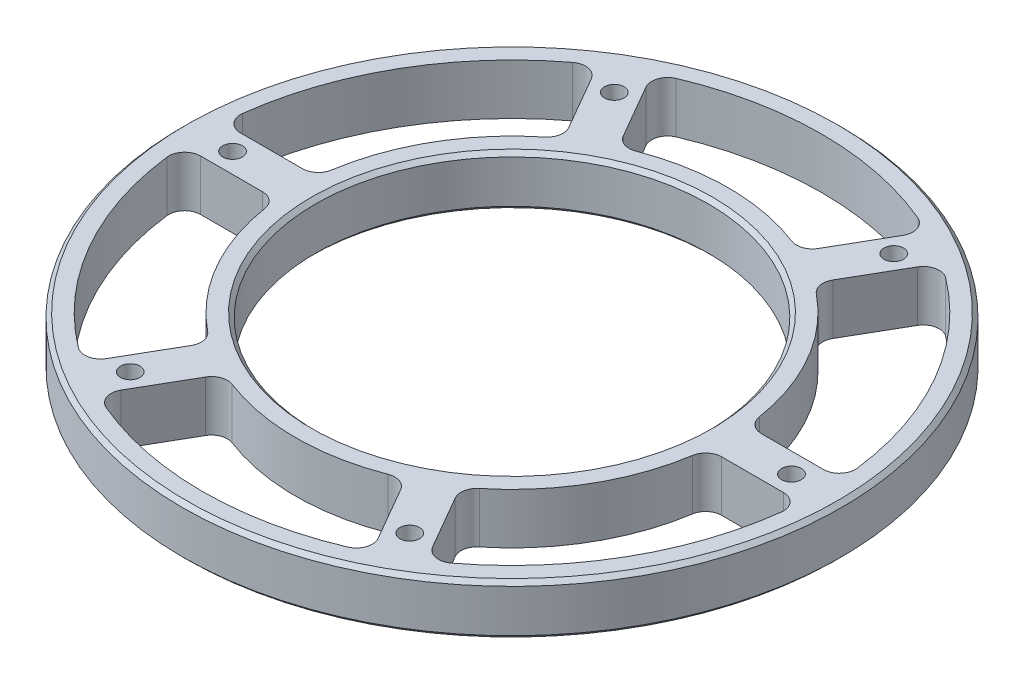
SolidWorks part; units mm, degrees
material "6061-T6 (SS)"
ref_plane "Front Plane" through (0, 0, 0) normal (0, 0, 1) x (1, 0, 0)
ref_plane "Top Plane" through (0, 0, 0) normal (0, 1, 0) x (1, 0, 0)
ref_plane "Right Plane" through (0, 0, 0) normal (1, 0, 0) x (0, 0, -1)
sketch "Sketch2" plane through (0, 0, 0) normal (1, 0, 0) x (0, 0, -1)
  line L0 (-49.2125, 0) -> (-82.55, 0)
  line L1 (-82.55, 0) -> (-82.55, 12.7)
  line L2 (-82.55, 12.7) -> (-49.2125, 12.7)
  line L3 (-49.2125, 12.7) -> (-49.2125, 0)
  dimension "D1" = 82.55
  dimension "D2" = 12.7
  dimension "D4" = 49.2125
ref_axis "Axis1" through (0, -0.635, 0) along (0, 1, 0)
revolve "Revolve1" add sketch "Sketch2" angle 360 about axis through (0, -0.635, 0) along (0, 1, 0)
hole_wizard "#10 (0.1935) Diameter Hole1" positions "Sketch6" profile "Sketch7" hole size "#10" standard "ANSI Inch" end condition through all
sketch "Sketch6" plane through (0, 12.7, 0) normal (0, 1, 0) x (1, 0, 0)
  line L0 (0, 0) -> (-69.8201, 120.932) construction
  line L2 (0, 0) -> (0, 109.0908) construction
  point P0 (-35, 60.6218)
  dimension "D1" = 30
  dimension "D2" = 70
sketch "Sketch7" plane through (-35, 12.7, -60.6218) normal (1, 0, 0) x (0, 0, 1)
  line L0 (0, 0) -> (0, 12.7)
  line L1 (0, 12.7) -> (2.4574, 12.7)
  line L2 (2.4574, 12.7) -> (2.4574, 0)
  line L5 (2.4574, 0) -> (0, 0)
  line L11 (0, -6.35) -> (0, 107.95) construction
  dimension "Thru Hole Dia." = 4.9149
  dimension "Thru Hole Depth" = 12.7
pattern_circular "CirPattern3" count 6 over 360 about axis through (0, -0.635, 0) along (0, 1, 0) of "#10 (0.1935) Diameter Hole1"
sketch "Sketch8" plane through (0, 12.7, 0) normal (0, 1, 0) x (1, 0, 0)
  line L4 (0, 0) -> (0, 93.9995) construction
  line L5 (-22.6606, 49.2493) -> (-34.3642, 69.5205)
  line L6 (22.6606, 49.2493) -> (34.3642, 69.5205)
  line L7 (0, 0) -> (-35, 60.6218) construction
  arc A0 (-22.6606, 49.2493) -> (22.6606, 49.2493) centre (0, 0) cw
  arc A1 (-34.3642, 69.5205) -> (34.3642, 69.5205) centre (0, 0) cw
  circle A2 centre (0, 0) radius 82.55 construction
  circle A4 centre (0, 0) radius 49.2125 construction
  dimension "D1" = 5
  dimension "D2" = 5
  dimension "D3" = 5
extrude "Cut-Extrude1" cut sketch "Sketch8" against normal through all
fillet "Fillet1" radius 4 4 edges at (-22.6606, 6.35, -49.2493) (22.6606, 6.35, -49.2493) (34.3642, 6.35, -69.5205) (-34.3642, 6.35, -69.5205)
pattern_circular "CirPattern4" count 6 over 360 about axis through (0, -0.635, 0) along (0, 1, 0) of "Cut-Extrude1", "Fillet1"
chamfer "Chamfer1" distance 1 angle 45 2 edges at (0, 12.7, -49.2125) (0, 0, -49.2125)
chamfer "Chamfer2" distance 1 angle 45 2 edges at (0, 12.7, -82.55) (0, 0, -82.55)
equation "\"TubeDiameter\" = 6.500in"
equation "\"D1@Sketch2\"=\"TubeDiameter\"/2"
